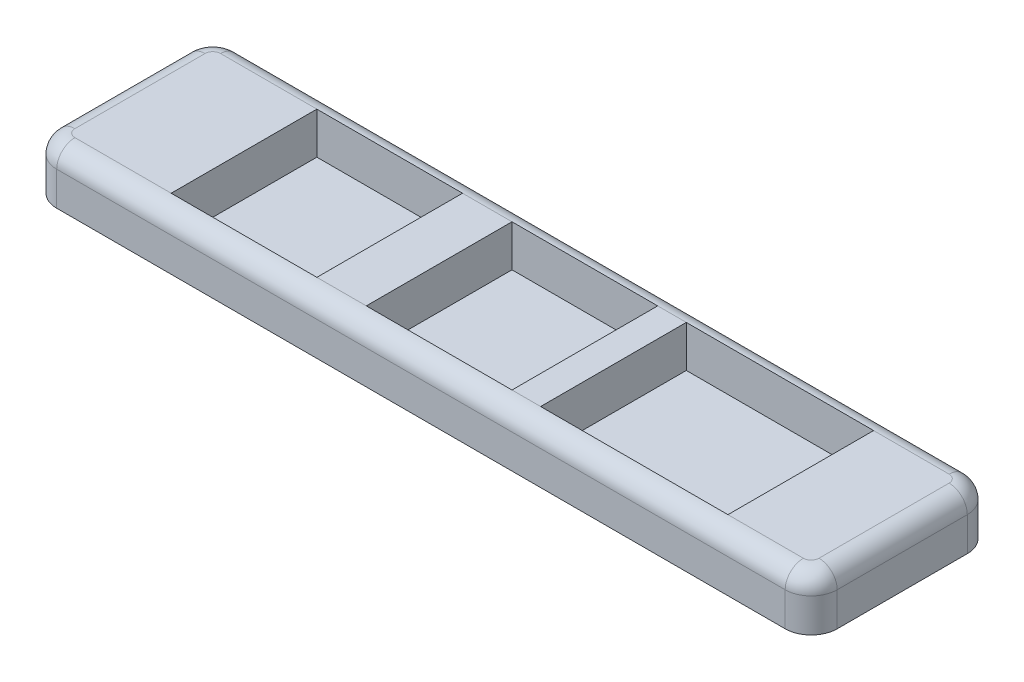
SolidWorks part; units mm, degrees
ref_plane "Front Plane" through (0, 0, 0) normal (0, 0, 1) x (1, 0, 0)
ref_plane "Top Plane" through (0, 0, 0) normal (0, 1, 0) x (1, 0, 0)
ref_plane "Right Plane" through (0, 0, 0) normal (1, 0, 0) x (0, 0, -1)
sketch "Sketch1" plane through (0, 0, 0) normal (0, 1, 0) x (1, 0, 0)
  line L0 (0, 17.5) -> (0, -17.5) construction
  line L1 (-75, -17.5) -> (75, -17.5)
  line L2 (-75, -17.5) -> (-75, 17.5)
  line L3 (-75, 17.5) -> (75, 17.5)
  line L4 (75, -17.5) -> (75, 17.5)
  line L5 (-75, -17.5) -> (75, 17.5) construction
  line L6 (-75, 17.5) -> (75, -17.5) construction
  line L7 (-75, 0) -> (0, 0) construction
  line L8 (0, 0) -> (75, 0) construction
  line L9 (-37.5, 0) -> (-37.5, 17.5) construction
  line L10 (-37.5, 17.5) -> (-37.5, -17.5) construction
  line L11 (37.5, 0) -> (37.5, 13.893) construction
  line L12 (37.5, 13.893) -> (37.5, -17.5) construction
  line L14 (-14, -14) -> (14, -14)
  line L15 (-14, -14) -> (-14, 14)
  line L16 (-14, 14) -> (14, 14)
  line L17 (14, -14) -> (14, 14)
  line L18 (-14, -14) -> (14, 14) construction
  line L19 (-14, 14) -> (14, -14) construction
  line L20 (-51.5, -14) -> (-23.5, -14)
  line L21 (-51.5, -14) -> (-51.5, 14)
  line L22 (-51.5, 14) -> (-23.5, 14)
  line L23 (-23.5, -14) -> (-23.5, 14)
  line L24 (-51.5, -14) -> (-23.5, 14) construction
  line L25 (-51.5, 14) -> (-23.5, -14) construction
  line L26 (19.5, -14) -> (55.5, -14)
  line L27 (19.5, -14) -> (19.5, 14)
  line L28 (19.5, 14) -> (55.5, 14)
  line L29 (55.5, -14) -> (55.5, 14)
  line L30 (19.5, -14) -> (55.5, 14) construction
  line L31 (19.5, 14) -> (55.5, -14) construction
  point P0 (0, 0)
  point P14 (-37.5, 0)
  dimension "D1" = 35
  dimension "D2" = 150
  dimension "D3" = 28
  dimension "D4" = 28
  dimension "D5" = 28
  dimension "D6" = 28
  dimension "D7" = 36
  dimension "D8" = 28
extrude "Boss-Extrude1" add sketch "Sketch1" along normal blind 10
sketch "Sketch2" plane through (0, 0, 0) normal (0, -1, 0) x (1, 0, 0)
  line L0 (-51.5, 14) -> (-23.5, 14) construction
  line L1 (-51.5, 14) -> (-23.5, 14)
  line L2 (-51.5, 14) -> (-51.5, -14)
  line L3 (-51.5, -14) -> (-23.5, -14)
  line L4 (-23.5, 14) -> (-23.5, -14)
  line L5 (-51.5, -14) -> (-51.5, 14) construction
  line L6 (-14, -14) -> (-14, 14) construction
  line L7 (-14, 14) -> (14, 14)
  line L8 (-14, 14) -> (-14, -14)
  line L9 (-14, -14) -> (14, -14)
  line L10 (14, 14) -> (14, -14)
  line L11 (14, 14) -> (14, -14) construction
  line L13 (19.5, 14) -> (55.5, 14)
  line L14 (19.5, 14) -> (19.5, -14)
  line L15 (19.5, -14) -> (55.5, -14)
  line L16 (55.5, 14) -> (55.5, -14)
extrude "Boss-Extrude2" add sketch "Sketch2" against normal blind 2
fillet "Fillet3" radius 3.5 4 edges at (-75, 10, 0) (0, 10, -17.5) (75, 10, 0) (0, 10, 17.5)
fillet "Fillet4" radius 5 8 edges at (73.9749, 8.9749, -16.4749) (-73.9749, 8.9749, -16.4749) (-73.9749, 8.9749, 16.4749) (73.9749, 8.9749, 16.4749) (75, 3.25, 17.5) (-75, 3.25, 17.5) (-75, 3.25, -17.5) (75, 3.25, -17.5)
